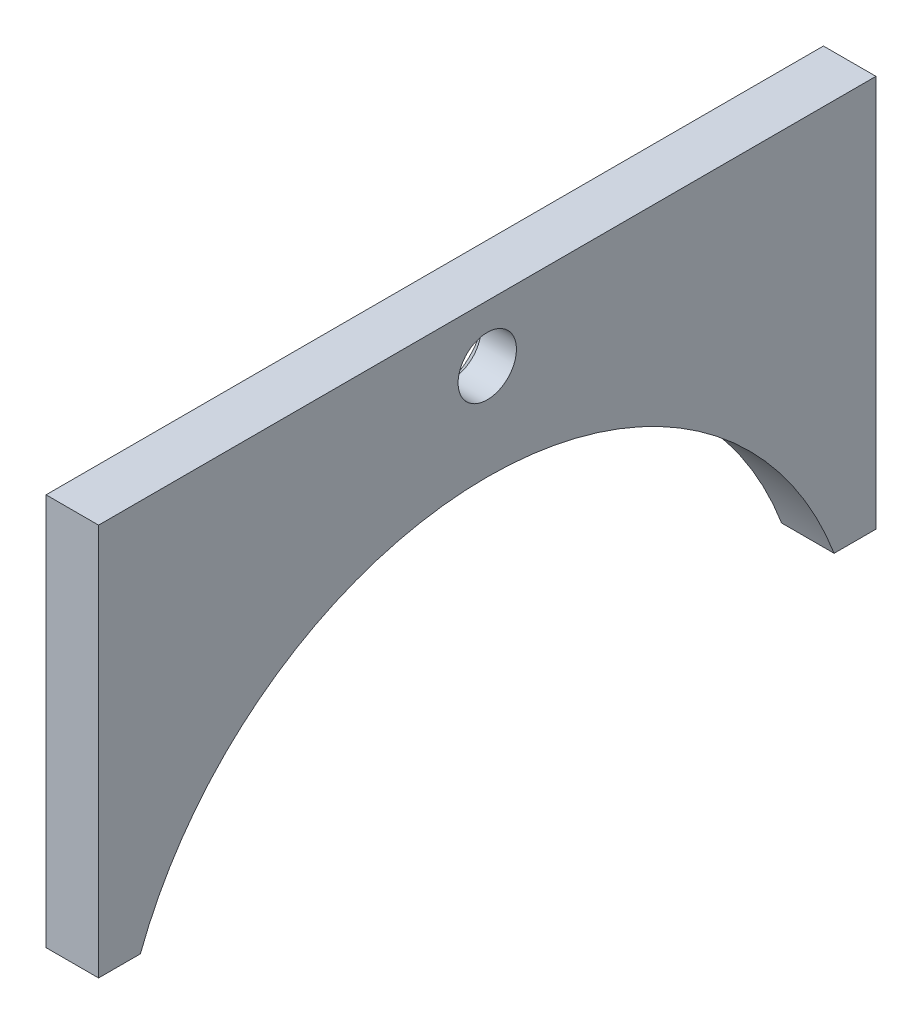
SolidWorks part; units mm, degrees
material "6061-T4 (SS)"
ref_plane "Front Plane" through (0, 0, 0) normal (0, 0, 1) x (1, 0, 0)
ref_plane "Top Plane" through (0, 0, 0) normal (0, 1, 0) x (1, 0, 0)
ref_plane "Right Plane" through (0, 0, 0) normal (1, 0, 0) x (0, 0, -1)
sketch "Sketch1" plane through (0, 0, 0) normal (0, 0, 1) x (1, 0, 0)
  line L1 (-3.3502, 4) -> (-1.75, 4)
  line L2 (-3.3502, 4) -> (-3.3502, 15.95)
  line L3 (-3.3502, 15.95) -> (-1.75, 15.95)
  line L4 (-1.75, 4) -> (-1.75, 15.95)
extrude "Boss-Extrude1" add sketch "Sketch1" along normal up to surface (23.6854 mm away)
sketch "Sketch2" plane through (-1.75, 0, 0) normal (1, 0, 0) x (0, 0, -1)
  line L0 (-23.6854, 4) -> (0, 4) construction
  line L1 (-22.4111, 4) -> (-1.2744, 4)
  arc A0 (-1.2744, 4) -> (-22.4111, 4) centre (-11.8427, 0) ccw
  arc A1 (-1.2744, 4) -> (-22.4111, 4) centre (-11.8427, 0) ccw construction
extrude "Cut-Extrude1" cut sketch "Sketch2" against normal blind 10
sketch "Sketch3" plane through (-1.75, 0, 0) normal (1, 0, 0) x (0, 0, -1)
  point P0 (-11.8427, 14.225)
hole_wizard "CSK for #0 Flat Head Machine Screw (100)1" positions "Sketch4" profile "Sketch5" countersink size "#0" standard "ANSI Inch"
sketch "Sketch4" plane through (-3.3502, 0, 0) normal (-1, 0, 0) x (0, 0, 1)
  point P0 (11.8427, 14.225)
  point P3 (0, 0)
sketch "Sketch5" plane through (-3.3502, 14.225, 11.8427) normal (0, 1, 0) x (0, 0, 1)
  line L0 (0, 0) -> (0, 3.5342)
  line L1 (0, 3.5342) -> (0.889, 3)
  line L2 (0.889, 3) -> (0.889, 0.5222)
  line L3 (0.889, 0.5222) -> (1.5113, 0)
  line L5 (1.5113, 0) -> (0, 0)
  line L6 (-0.889, 0.5222) -> (-1.5113, 0) construction
  line L10 (0, 3.5342) -> (-0.889, 3) construction
  line L11 (0, -6.35) -> (0, 107.95) construction
  dimension "Hole Dia." = 1.778
  dimension "Hole Depth" = 3
  dimension "Near C'Sink Dia." = 3.0226
  dimension "Near C'Sink Angle" = 100
  dimension "Drill Angle" = 118
